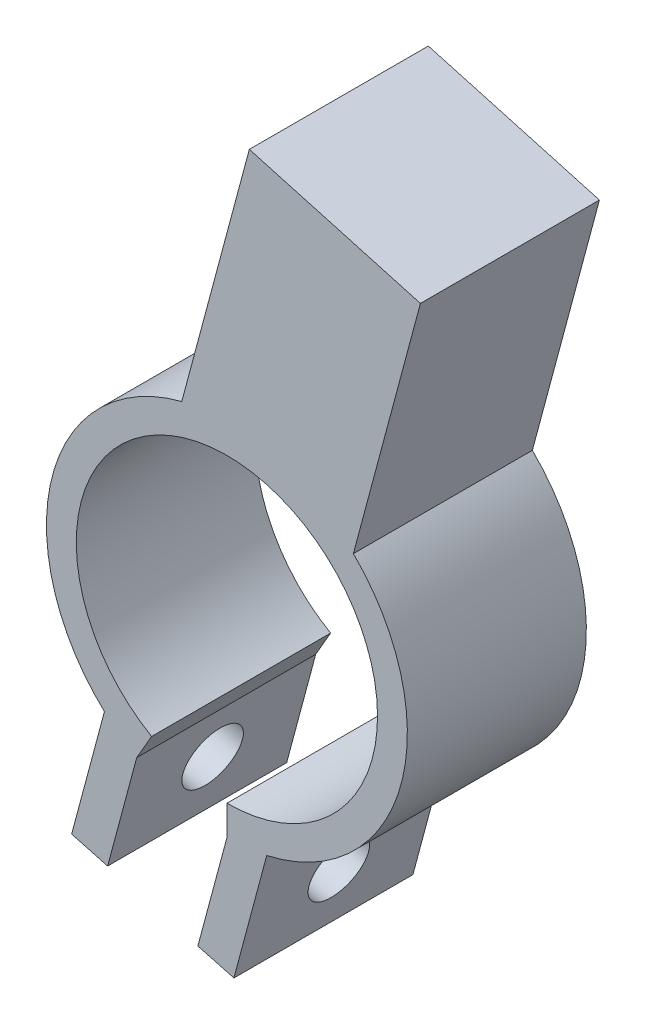
SolidWorks part; units mm, degrees
ref_plane "Front Plane" through (0, 0, 0) normal (0, 0, 1) x (1, 0, 0)
ref_plane "Top Plane" through (0, 0, 0) normal (0, 1, 0) x (1, 0, 0)
ref_plane "Right Plane" through (0, 0, 0) normal (1, 0, 0) x (0, 0, -1)
sketch "Sketch1" plane through (0, 0, 0) normal (0, 0, 1) x (1, 0, 0)
  circle A0 centre (0, 0) radius 20.193
  circle A1 centre (0, 0) radius 20.193 construction
  circle A2 centre (0, 0) radius 24.193
  dimension "D1" = 4
extrude "Boss-Extrude1" add sketch "Sketch1" along normal blind 24
sketch "Sketch2" plane through (0, 0, 24) normal (0, 0, 1) x (1, 0, 0)
  line L0 (0, -24.193) -> (-5.8342, -24.8953)
  line L1 (-5.8342, -24.8953) -> (-12.0965, -20.9518)
  line L2 (0, -24.193) -> (0, 0)
  line L3 (-12.0965, -20.9518) -> (0, 0)
  circle A0 centre (0, 0) radius 24.193 construction
  dimension "D1" = 7.4005
  dimension "D2" = 5.8342
  dimension "D3" = 30
extrude "Cut-Extrude1" cut sketch "Sketch2" against normal blind 24
sketch "Sketch3" plane through (0, 0, 24) normal (0, 0, 1) x (1, 0, 0)
  line L0 (-12.0965, -20.9518) -> (-15.99, -35.4826)
  line L1 (-15.99, -35.4826) -> (-20.8197, -34.1885)
  line L2 (-20.8197, -34.1885) -> (-16.4197, -17.7678)
  line L3 (-12.0965, -20.9518) -> (-16.4197, -17.7678)
  line L4 (0, -24.193) -> (5.336, -23.5972)
  line L5 (5.336, -23.5972) -> (0.9361, -40.0179)
  line L6 (0.9361, -40.0179) -> (-3.8935, -38.7238)
  line L7 (-3.8935, -38.7238) -> (0, -24.193)
  line L8 (-3.8935, -38.7238) -> (-15.99, -35.4826)
  line L9 (0, -24.193) -> (-12.0965, -20.9518)
  arc A0 (0, -24.193) -> (-12.0965, -20.9518) centre (0, 0) ccw construction
  point P13 (0, 0)
  point P14 (-21.5456, -33.0792)
  arc M6 (0, -24.193) -> (-12.0965, -20.9518) centre (0, 0) ccw
  dimension "D1" = 17
  dimension "D2" = 5
extrude "Boss-Extrude2" add sketch "Sketch3" against normal blind 24 contours L2 L1 L0 M6 | L7 L6 L5 M6 region at (-16.3921, -27.1264, 24) region at (0.6327, -31.6882, 24)
sketch "Sketch4" plane through (-10.8779, 2.9147, 0) normal (-0.9659, 0.2588, 0) x (0, 0, 1)
  line L0 (12, -38.4121) -> (12, -30.4121)
  line L1 (0, -38.4121) -> (24, -38.4121) construction
  circle A0 centre (12, -30.4121) radius 4
  point P3 (12, -29.834)
  dimension "D2" = 8
  dimension "D1" = 8
extrude "Cut-Extrude2" cut sketch "Sketch4" against normal blind 24 contours A0 region at (-19.4605, -29.1159, 14.7484)
sketch "Sketch5" plane through (0, 0, 24) normal (0, 0, 1) x (1, 0, 0)
  line L0 (0, -20.193) -> (-10.0965, -17.4877)
  line L3 (16.9534, 17.2593) -> (25.9449, 50.816)
  line L4 (25.9449, 50.816) -> (3.0062, 57.2311)
  line L5 (3.0062, 57.2311) -> (-6.0524, 23.4237)
  line L6 (16.9534, 17.2593) -> (-6.0524, 23.4237)
  arc A0 (5.336, -23.5972) -> (-16.4197, -17.7678) centre (0, 0) ccw construction
  arc M14 (5.336, -23.5972) -> (-16.4197, -17.7678) centre (0, 0) ccw
  dimension "D1" = 35
extrude "Boss-Extrude4" add sketch "Sketch5" against normal blind 24 contours L4 L5 L3 M14 region at (10.2186, 38.197, 24)
